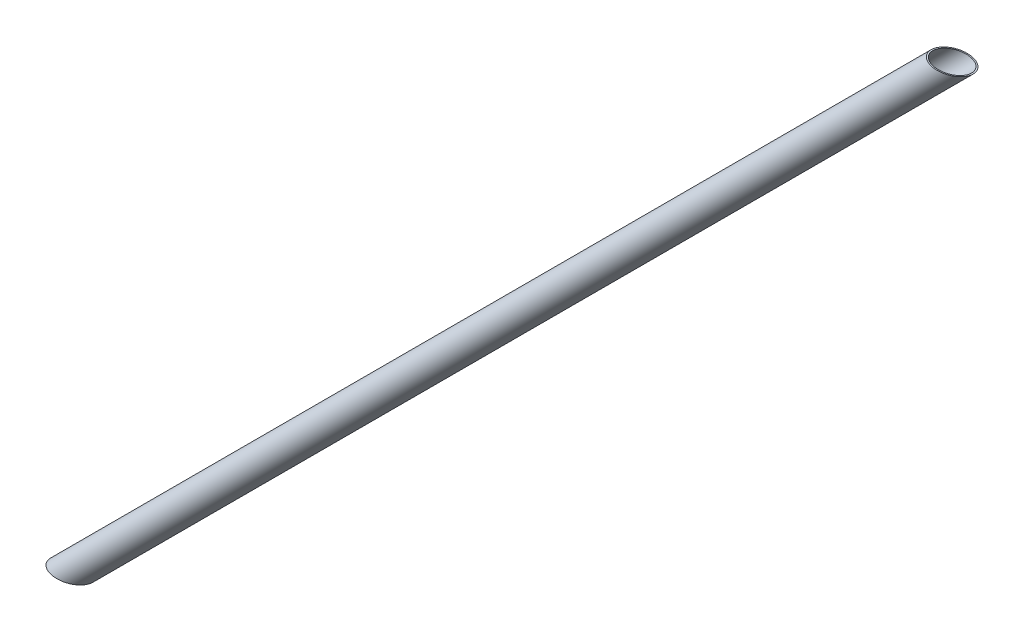
SolidWorks part; units mm, degrees
ref_plane "Alzado" through (0, 0, 0) normal (0, 0, 1) x (1, 0, 0)
ref_plane "Planta" through (0, 0, 0) normal (0, 1, 0) x (1, 0, 0)
ref_plane "Vista lateral" through (0, 0, 0) normal (1, 0, 0) x (0, 0, -1)
sketch "Croquis1" plane through (0, 0, 0) normal (0, 0, 1) x (1, 0, 0)
  line L1 (1500, 1500) -> (1500, 0) construction
  line L2 (0, 0) -> (1500, 0) construction
  line L3 (0, -35.921) -> (-1.4142, -34.5068)
  line L14 (1500, 1500) -> (1517.9605, 1482.0395) construction
  line L16 (1517.9605, 1482.0395) -> (1535.921, 1500) construction
  line L19 (1535.921, 1500) -> (1517.9605, 1517.9605) construction
  line L20 (1517.9605, 1517.9605) -> (0, 0) construction
  line L21 (1500, 1500) -> (1535.921, 1500) construction
  line L22 (1535.921, 1500) -> (0, -35.921)
  line L24 (-1.4142, -34.5068) -> (1534.5068, 1501.4142)
  line L25 (1534.5068, 1501.4142) -> (1535.921, 1500)
  line L26 (0, 0) -> (0, -35.921) construction
  line L27 (0, 0) -> (-17.9605, -17.9605) construction
  line L28 (-17.9605, -17.9605) -> (0, -35.921) construction
  dimension "D1" = 1500
  dimension "D2" = 1500
  dimension "D4" = 90
  dimension "D5" = 25.4
  dimension "D6" = 90
  dimension "D8" = 2
  dimension "D9" = 45
  dimension "D10" = 25.4
  dimension "D11" = 90
revolve "Revolución1" add sketch "Croquis1" angle 360 about L20
sketch "Croquis2" plane through (0, 0, 0) normal (0, 0, 1) x (1, 0, 0)
  line L0 (-35.921, 0) -> (35.921, 0)
  line L1 (0, -35.921) -> (1535.921, 1500) construction
  line L2 (35.921, 0) -> (0, -35.921)
  line L3 (0, -35.921) -> (-35.921, 0)
  line L4 (1535.921, 1500) -> (1464.079, 1500)
  line L5 (1500, 1535.921) -> (-35.921, 0) construction
  line L6 (1464.079, 1500) -> (1500, 1535.921)
  line L7 (1500, 1535.921) -> (1535.921, 1500)
extrude "Cortar-Extruir1" cut sketch "Croquis2" against normal through all and the other way through all contours L3 L0 L2 | L7 L4 L6
